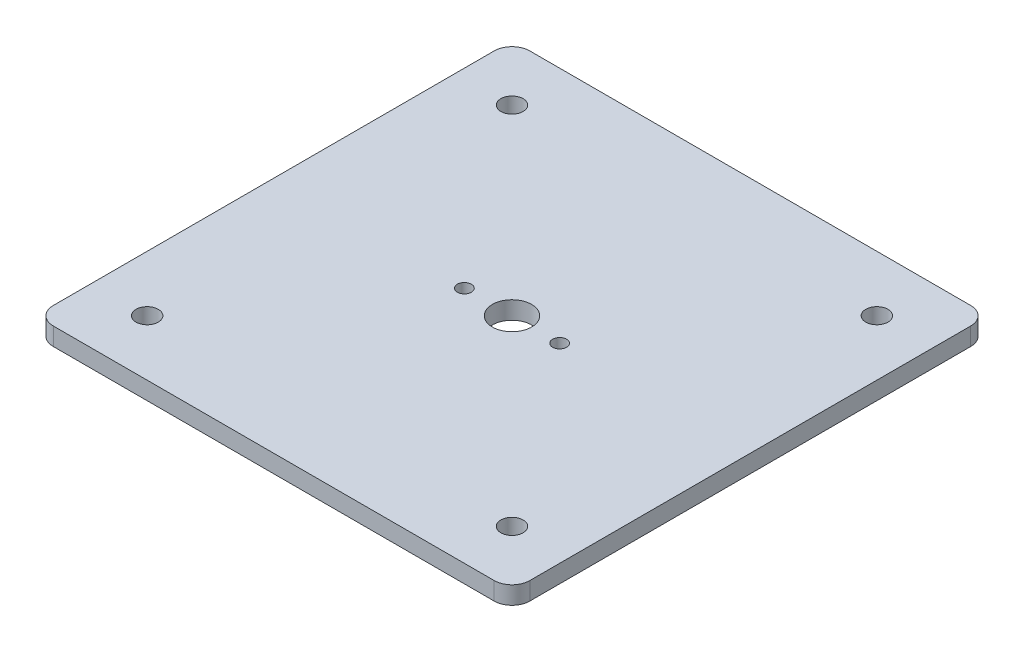
SolidWorks part; units mm, degrees
material "6061 Alloy"
ref_plane "Front Plane" through (0, 0, 0) normal (0, 0, 1) x (1, 0, 0)
ref_plane "Top Plane" through (0, 0, 0) normal (0, 1, 0) x (1, 0, 0)
ref_plane "Right Plane" through (0, 0, 0) normal (1, 0, 0) x (0, 0, -1)
ref_plane "Plane1" through (0, 0, 0) normal (0, 1, 0) x (1, 0, 0)
sketch "Sketch1" plane through (0, 0, 0) normal (0, 1, 0) x (1, 0, 0)
  line L1 (0, 0) -> (85, 0)
  line L2 (0, 0) -> (0, 85)
  line L3 (0, 85) -> (85, 85)
  line L4 (85, 0) -> (85, 85)
  dimension "D1" = 85
  dimension "D2" = 85
extrude "Boss-Extrude1" add sketch "Sketch1" along normal blind 3.175
ref_plane "Plane2" through (0, 3.175, 0) normal (0, 1, 0) x (1, 0, 0)
sketch "Sketch2" plane through (0, 3.175, 0) normal (0, 1, 0) x (1, 0, 0)
  line L0 (85, 85) -> (0, 85) construction
  line L1 (0, 85) -> (0, 0) construction
  circle A0 centre (9.955, 75.045) radius 1.985
  dimension "D1" = 3.97
  dimension "D2" = 9.955
  dimension "D3" = 9.955
extrude "Cut-Extrude1" cut sketch "Sketch2" against normal through all
pattern_linear "LPattern1" count 2 spacing 65.09 along (0, 0, 1) count 2 spacing 65.09 along (1, 0, 0) of "Cut-Extrude1"
fillet "Fillet1" radius 3.175 4 edges at (0, 1.5875, 0) (85, 1.5875, 0) (85, 1.5875, -85) (0, 1.5875, -85)
sketch "Sketch3" plane through (0, 3.175, 0) normal (0, 1, 0) x (1, 0, 0)
  line L0 (3.175, 0) -> (81.825, 0) construction
  line L1 (85, 3.175) -> (85, 81.825) construction
  circle A0 centre (42.5, 42.5) radius 3.5
  point P2 (34, 42.5)
  point P3 (51, 42.5)
  dimension "D1" = 7
  dimension "D2" = 42.5
  dimension "D3" = 42.5
  dimension "D4" = 8.5
  dimension "D5" = 8.5
extrude "Cut-Extrude2" cut sketch "Sketch3" against normal through all
hole_wizard "M3x0.5 Tapped Hole1" positions "Sketch6" profile "Sketch7" tap size "M3x0.5" standard "ANSI Metric" end condition through all
sketch "Sketch6" plane through (0, 3.175, 0) normal (0, 1, 0) x (1, 0, 0)
  point P0 (34, 42.5)
  point P3 (51, 42.5)
sketch "Sketch7" plane through (34, 3.175, -42.5) normal (1, 0, 0) x (0, 0, 1)
  line L0 (0, 0) -> (0, 3.175)
  line L1 (0, 3.175) -> (1.25, 3.175)
  line L2 (1.25, 3.175) -> (1.25, 0)
  line L5 (1.25, 0) -> (0, 0)
  line L11 (0, -6.35) -> (0, 107.95) construction
  dimension "Thru Tap Drill Dia." = 2.5
  dimension "Thru Tap Drill Depth" = 3.175
